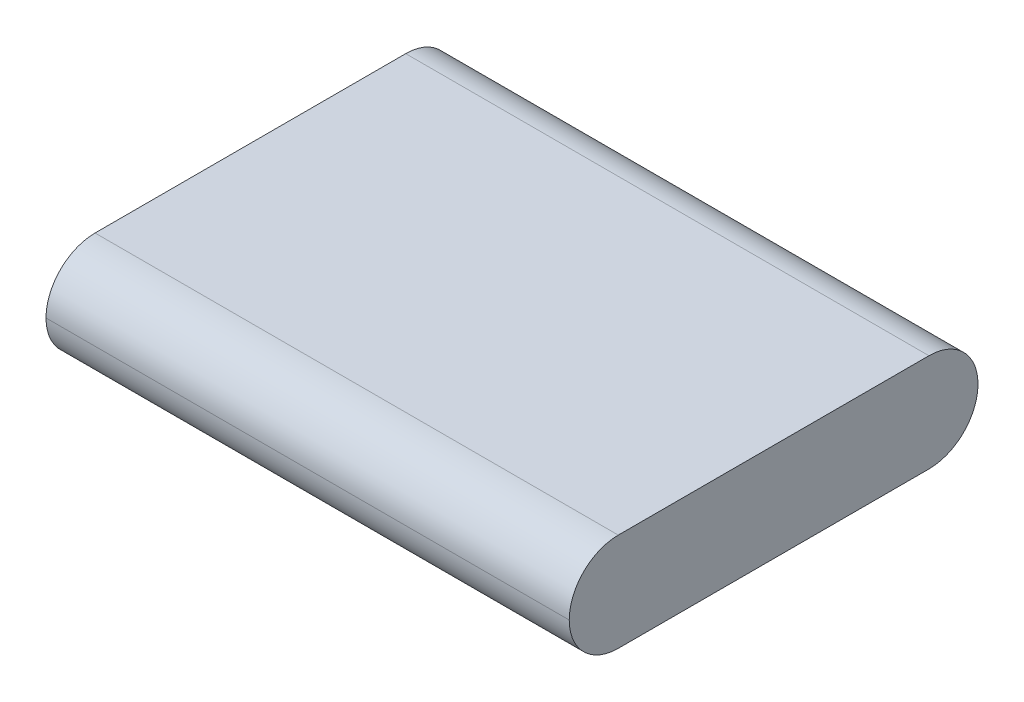
SolidWorks part; units mm, degrees
ref_plane "前视基准面" through (0, 0, 0) normal (0, 0, 1) x (1, 0, 0)
ref_plane "上视基准面" through (0, 0, 0) normal (0, 1, 0) x (1, 0, 0)
ref_plane "右视基准面" through (0, 0, 0) normal (1, 0, 0) x (0, 0, -1)
sketch "草图1" plane through (0, 0, 0) normal (0, 1, 0) x (1, 0, 0)
  line L1 (-16, 12.5) -> (16, 12.5)
  line L2 (-16, 12.5) -> (-16, -12.5)
  line L3 (-16, -12.5) -> (16, -12.5)
  line L4 (16, 12.5) -> (16, -12.5)
  dimension "D1" = 32
  dimension "D2" = 25
  dimension "D3" = 16
  dimension "D4" = 12.5
extrude "凸台-拉伸1" add sketch "草图1" along normal blind 6
fillet "圆角1" radius 3 4 edges at (0, 0, -12.5) (0, 6, -12.5) (0, 6, 12.5) (0, 0, 12.5)
